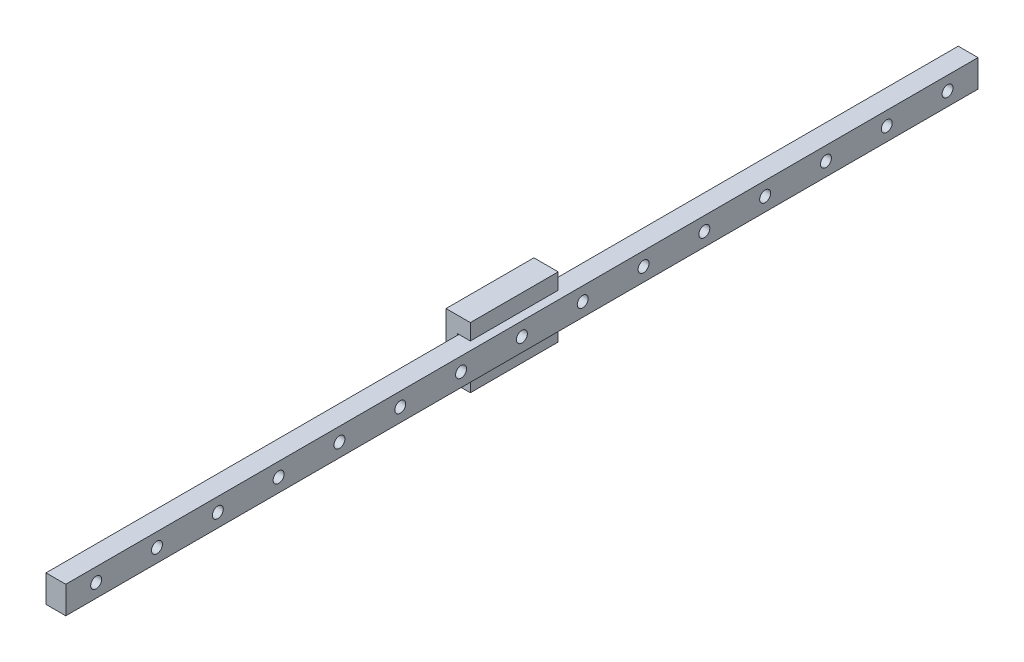
SolidWorks part; units mm, degrees
ref_plane "Front Plane" through (0, 0, 0) normal (0, 0, 1) x (1, 0, 0)
ref_plane "Top Plane" through (0, 0, 0) normal (0, 1, 0) x (1, 0, 0)
ref_plane "Right Plane" through (0, 0, 0) normal (1, 0, 0) x (0, 0, -1)
sketch "Sketch1" plane through (0, 0, 0) normal (0, 0, 1) x (1, 0, 0)
  line L1 (3.25, 4.5) -> (-3.25, 4.5)
  line L2 (3.25, 4.5) -> (3.25, -4.5)
  line L3 (3.25, -4.5) -> (-3.25, -4.5)
  line L4 (-3.25, 4.5) -> (-3.25, -4.5)
  line L5 (0, -4.5) -> (0, 4.5) construction
  line L6 (3.25, 0) -> (-3.25, 0) construction
  point P0 (0, 0)
  dimension "D1" = 6.5
  dimension "D2" = 9
extrude "Boss-Extrude1" add sketch "Sketch1" along normal mid plane 300
sketch "Sketch2" plane through (0, 0, 0) normal (0, 0, 1) x (1, 0, 0)
  line L0 (3.25, -4.5) -> (3.25, 4.5) construction
  line L1 (0.75, 10) -> (-7.25, 10)
  line L2 (0.75, 10) -> (0.75, -10)
  line L3 (0.75, -10) -> (-7.25, -10)
  line L4 (-7.25, 10) -> (-7.25, -10)
  line L5 (-3.25, -10) -> (-3.25, 10) construction
  line L6 (0.75, 0) -> (-7.25, 0) construction
  line L7 (0.75, 4.75) -> (-3.45, 4.75)
  line L8 (0.75, 4.75) -> (0.75, -4.75)
  line L9 (0.75, -4.75) -> (-3.45, -4.75)
  line L10 (-3.45, 4.75) -> (-3.45, -4.75)
  line L11 (-1.35, -4.75) -> (-1.35, 4.75) construction
  line L12 (0.75, 0) -> (-3.45, 0) construction
  line L13 (-3.25, 4.5) -> (-3.25, -4.5) construction
  point P144 (-1.35, 0)
  point P340 (-3.25, 0)
  dimension "D1" = 8
  dimension "D2" = 2.5
  dimension "D3" = 0.2
  dimension "D4" = 9.5
  dimension "D5" = 20
extrude "Boss-Extrude2" add sketch "Sketch2" along normal mid plane 28.9 separate body contours L10 L7 L2 L1 L4 L3 L9 region at (-3.8812, 0, 0)
hole_wizard "M3x0.5 Tapped Hole1" positions "Sketch3" profile "Sketch4" tap size "M3x0.5" standard "ANSI Metric"
sketch "Sketch3" plane through (-7.25, 0, 0) normal (-1, 0, 0) x (0, 0, 1)
  line L1 (-5, 7.5) -> (5, 7.5)
  line L2 (-5, 7.5) -> (-5, -7.5)
  line L3 (-5, -7.5) -> (5, -7.5)
  line L4 (5, 7.5) -> (5, -7.5)
  line L5 (0, -7.5) -> (0, 7.5) construction
  line L6 (-5, 0) -> (5, 0) construction
  point P5 (-5, 7.5)
  point P6 (5, -7.5)
  point P259 (-5, -7.5)
  point P260 (5, 7.5)
  dimension "D1" = 10
  dimension "D2" = 15
sketch "Sketch4" plane through (-7.25, 7.5, -5) normal (0, 1, 0) x (0, 0, 1)
  line L0 (0, 0) -> (0, 3.7511)
  line L1 (0, 3.7511) -> (1.25, 3)
  line L2 (1.25, 3) -> (1.25, 0)
  line L5 (1.25, 0) -> (0, 0)
  line L10 (0, 3.7511) -> (-1.25, 3) construction
  line L11 (0, -6.35) -> (0, 107.95) construction
  dimension "Tap Drill Dia." = 2.5
  dimension "Tap Drill Depth" = 3
  dimension "Drill Angle" = 118
hole_wizard "CBORE for M3 SHCS1" positions "Sketch5" profile "Sketch6" counterbore size "M3" standard "ANSI Metric" end condition through all
sketch "Sketch5" plane through (-3.25, 0, 0) normal (-1, 0, 0) x (0, 0, 1)
  line L0 (-150, 0) -> (-140, 0) construction
  line L1 (-150, 4.5) -> (-150, -4.5) construction
  point P0 (-140, 0)
  dimension "D1" = 10
sketch "Sketch6" plane through (-3.25, 0, -140) normal (0, 1, 0) x (0, 0, 1)
  line L0 (0, 0) -> (0, 6.5)
  line L1 (0, 6.5) -> (1.8, 6.5)
  line L3 (1.8, 6.5) -> (1.8, 3)
  line L4 (1.8, 3) -> (3.25, 3)
  line L5 (3.25, 3) -> (3.25, 0)
  line L7 (3.25, 0) -> (0, 0)
  line L11 (0, -6.35) -> (0, 107.95) construction
  dimension "Thru Hole Dia." = 3.6
  dimension "Thru Hole Depth" = 6.5
  dimension "C'Bore Dia." = 6.5
  dimension "C'Bore Depth" = 3
pattern_linear "LPattern1" count 15 spacing 20 along (0, 0, 1) of "CBORE for M3 SHCS1"
